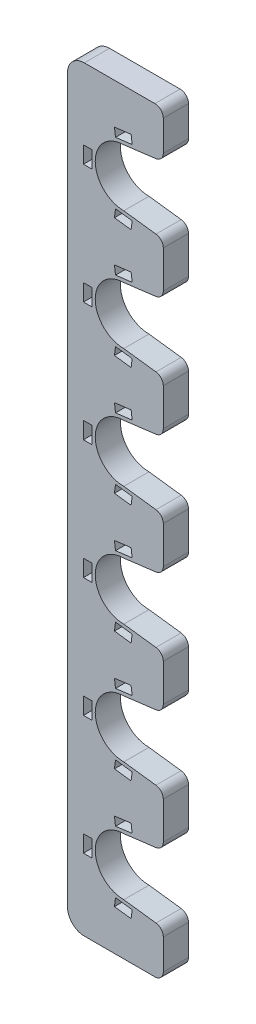
SolidWorks part; units mm, degrees
ref_plane "Front" through (0, 0, 0) normal (0, 0, 1) x (1, 0, 0)
ref_plane "Top" through (0, 0, 0) normal (0, 1, 0) x (1, 0, 0)
ref_plane "Right" through (0, 0, 0) normal (1, 0, 0) x (0, 0, -1)
sketch "Esquisse1" plane through (0, 0, 0) normal (0, 0, 1) x (1, 0, 0)
  line L1 (0, 0) -> (47, 0)
  line L2 (0, 0) -> (0, 450)
  line L3 (0, 450) -> (47, 450)
  line L4 (47, 0) -> (47, 450)
  dimension "D1" = 47
  dimension "D2" = 450
extrude "Boss.-Extru.1" add sketch "Esquisse1" along normal blind 15
sketch "Esquisse2" plane through (0, 0, 15) normal (0, 0, 1) x (1, 0, 0)
  line L0 (23.5, 0) -> (23.5, 450) construction
  line L1 (0, 0) -> (47, 0) construction
  line L2 (47, 450) -> (0, 450) construction
  line L3 (23.5, 225) -> (0, 225) construction
  line L4 (23.5, 154) -> (0, 154) construction
  line L5 (0, 450) -> (0, 0) construction
  line L6 (23.5, 83) -> (0, 83) construction
  line L7 (23.5, 367) -> (0, 367) construction
  line L8 (23.5, 296) -> (0, 296) construction
  circle A0 centre (23.5, 260.5) radius 17
  circle A1 centre (23.5, 189.5) radius 17
  circle A2 centre (23.5, 118.5) radius 17
  circle A3 centre (23.5, 47.5) radius 17
  circle A4 centre (23.5, 402.5) radius 17
  circle A5 centre (23.5, 331.5) radius 17
  dimension "D1" = 71
  dimension "D2" = 34
  dimension "D3" = 71
  dimension "D4" = 71
extrude "Enlèv. mat.-Extru.1" cut sketch "Esquisse2" against normal through all both and the other way through all
sketch "Esquisse3" plane through (0, 0, 15) normal (0, 0, 1) x (1, 0, 0)
  line L0 (23.5, 189.5) -> (23.5, 260.5) construction
  line L1 (23.5, 225) -> (0, 225) construction
  line L2 (0, 450) -> (0, 0) construction
  line L3 (23.5, 243.5) -> (47, 240.5)
  line L4 (47, 0) -> (47, 450) construction
  line L5 (47, 240.5) -> (47, 280.5)
  line L6 (47, 260.5) -> (23.5, 260.5) construction
  line L7 (23.5, 277.5) -> (47, 280.5)
  line L8 (23.5, 243.5) -> (23.5, 277.5)
  line L9 (47, 189.5) -> (23.5, 189.5) construction
  line L10 (23.5, 172.5) -> (47, 169.5)
  line L11 (47, 209.5) -> (47, 169.5)
  line L12 (23.5, 206.5) -> (47, 209.5)
  line L13 (23.5, 206.5) -> (23.5, 172.5)
  line L14 (23.5, 172.5) -> (23.5, 135.5) construction
  line L15 (23.5, 64.5) -> (23.5, 101.5) construction
  line L16 (23.5, 83) -> (0, 83) construction
  line L17 (23.5, 154) -> (0, 154) construction
  line L18 (47, 118.5) -> (23.5, 118.5) construction
  line L19 (23.5, 101.5) -> (23.5, 135.5)
  line L20 (23.5, 101.5) -> (47, 98.5)
  line L21 (47, 98.5) -> (47, 138.5)
  line L22 (23.5, 135.5) -> (47, 138.5)
  line L23 (47, 47.5) -> (23.5, 47.5) construction
  line L24 (23.5, 30.5) -> (47, 27.5)
  line L25 (47, 67.5) -> (47, 27.5)
  line L26 (23.5, 64.5) -> (47, 67.5)
  line L27 (23.5, 64.5) -> (23.5, 30.5)
  line L28 (47, 402.5) -> (23.5, 402.5) construction
  line L29 (47, 331.5) -> (23.5, 331.5) construction
  line L30 (23.5, 296) -> (0, 296) construction
  line L31 (23.5, 367) -> (0, 367) construction
  line L32 (23.5, 385.5) -> (23.5, 348.5) construction
  line L33 (23.5, 385.5) -> (23.5, 419.5)
  line L34 (23.5, 385.5) -> (47, 382.5)
  line L35 (47, 382.5) -> (47, 422.5)
  line L36 (23.5, 419.5) -> (47, 422.5)
  line L37 (23.5, 314.5) -> (47, 311.5)
  line L38 (47, 351.5) -> (47, 311.5)
  line L39 (23.5, 348.5) -> (47, 351.5)
  line L40 (23.5, 348.5) -> (23.5, 314.5)
  circle A0 centre (23.5, 260.5) radius 17 construction
  circle A1 centre (23.5, 118.5) radius 17 construction
  circle A2 centre (23.5, 47.5) radius 17 construction
  dimension "D1" = 3
extrude "Enlèv. mat.-Extru.2" cut sketch "Esquisse3" against normal through all both and the other way through all
sketch "Esquisse4" plane through (0, 0, 15) normal (0, 0, 1) x (1, 0, 0)
  line L0 (47, 450) -> (0, 450) construction
  line L1 (0, 0) -> (-10, 0)
  line L2 (0, 0) -> (0, 450)
  line L3 (0, 450) -> (-10, 450)
  line L4 (-10, 0) -> (-10, 450)
  dimension "D1" = 10
extrude "Boss.-Extru.2" add sketch "Esquisse4" against normal up to vertex (15 mm away) up to point (0, 450, 0)
sketch "Esquisse5" plane through (0, 0, 15) normal (0, 0, 1) x (1, 0, 0)
  line L0 (47, 367) -> (-10, 367) construction
  line L1 (47, 351.5) -> (47, 382.5) construction
  line L2 (-10, 450) -> (-10, 0) construction
  line L3 (47, 296) -> (-10, 296) construction
  line L4 (47, 280.5) -> (47, 311.5) construction
  line L5 (47, 225) -> (-10, 225) construction
  line L6 (47, 209.5) -> (47, 240.5) construction
  line L7 (47, 154) -> (-10, 154) construction
  line L8 (47, 138.5) -> (47, 169.5) construction
  line L9 (47, 83) -> (-10, 83) construction
  line L10 (47, 67.5) -> (47, 98.5) construction
  line L11 (4.5, 189.5) -> (6.5, 189.5) construction
  line L12 (-0.5, 194.5) -> (4.5, 194.5)
  line L13 (-0.5, 194.5) -> (-0.5, 184.5)
  line L14 (-0.5, 184.5) -> (4.5, 184.5)
  line L15 (4.5, 194.5) -> (4.5, 184.5)
  line L16 (47, 169.5) -> (47, 209.5) construction
  line L17 (47, 189.5) -> (6.5, 189.5) construction
  line L18 (18.564, 207.8861) -> (28.4835, 209.1524)
  line L19 (23.5, 206.5) -> (47, 209.5) construction
  line L20 (18.564, 207.8861) -> (17.9308, 212.8458)
  line L21 (17.9308, 212.8458) -> (27.8503, 214.1122)
  line L22 (27.8503, 214.1122) -> (28.4835, 209.1524)
  line L23 (18.564, 207.8861) -> (26.75, 189.5) construction
  line L24 (27.8503, 164.8878) -> (28.4835, 169.8476)
  line L25 (17.9308, 166.1542) -> (27.8503, 164.8878)
  line L26 (18.564, 171.1139) -> (17.9308, 166.1542)
  line L27 (18.564, 171.1139) -> (28.4835, 169.8476)
  line L28 (18.564, 100.1139) -> (26.75, 118.5) construction
  line L29 (47, 118.5) -> (6.5, 118.5) construction
  line L30 (47, 138.5) -> (47, 98.5) construction
  line L31 (4.5, 118.5) -> (6.5, 118.5) construction
  line L32 (18.564, 136.8861) -> (28.4835, 138.1524)
  line L33 (18.564, 136.8861) -> (17.9308, 141.8458)
  line L34 (17.9308, 141.8458) -> (27.8503, 143.1122)
  line L35 (27.8503, 143.1122) -> (28.4835, 138.1524)
  line L36 (27.8503, 93.8878) -> (28.4835, 98.8476)
  line L37 (17.9308, 95.1542) -> (27.8503, 93.8878)
  line L38 (18.564, 100.1139) -> (17.9308, 95.1542)
  line L39 (18.564, 100.1139) -> (28.4835, 98.8476)
  line L40 (4.5, 113.5) -> (4.5, 123.5)
  line L41 (-0.5, 123.5) -> (4.5, 123.5)
  line L42 (-0.5, 113.5) -> (-0.5, 123.5)
  line L43 (-0.5, 113.5) -> (4.5, 113.5)
  line L44 (4.5, 47.5) -> (6.5, 47.5) construction
  line L45 (47, 27.5) -> (47, 67.5) construction
  line L46 (47, 47.5) -> (6.5, 47.5) construction
  line L47 (18.564, 65.8861) -> (26.75, 47.5) construction
  line L48 (-0.5, 52.5) -> (4.5, 52.5)
  line L49 (-0.5, 52.5) -> (-0.5, 42.5)
  line L50 (-0.5, 42.5) -> (4.5, 42.5)
  line L51 (4.5, 52.5) -> (4.5, 42.5)
  line L52 (18.564, 65.8861) -> (28.4835, 67.1524)
  line L53 (18.564, 65.8861) -> (17.9308, 70.8458)
  line L54 (17.9308, 70.8458) -> (27.8503, 72.1122)
  line L55 (27.8503, 72.1122) -> (28.4835, 67.1524)
  line L56 (27.8503, 22.8878) -> (28.4835, 27.8476)
  line L57 (17.9308, 24.1542) -> (27.8503, 22.8878)
  line L58 (18.564, 29.1139) -> (17.9308, 24.1542)
  line L59 (18.564, 29.1139) -> (28.4835, 27.8476)
  line L60 (18.564, 384.1139) -> (26.75, 402.5) construction
  line L61 (47, 402.5) -> (6.5, 402.5) construction
  line L62 (47, 422.5) -> (47, 382.5) construction
  line L63 (4.5, 402.5) -> (6.5, 402.5) construction
  line L64 (4.5, 331.5) -> (6.5, 331.5) construction
  line L65 (47, 311.5) -> (47, 351.5) construction
  line L66 (47, 331.5) -> (6.5, 331.5) construction
  line L67 (18.564, 349.8861) -> (26.75, 331.5) construction
  line L68 (18.564, 242.1139) -> (26.75, 260.5) construction
  line L69 (47, 260.5) -> (6.5, 260.5) construction
  line L70 (47, 280.5) -> (47, 240.5) construction
  line L71 (4.5, 260.5) -> (6.5, 260.5) construction
  line L72 (47, 367) -> (-10, 367) construction
  line L73 (47, 296) -> (-10, 296) construction
  line L74 (18.564, 420.8861) -> (28.4835, 422.1524)
  line L75 (18.564, 420.8861) -> (17.9308, 425.8458)
  line L76 (17.9308, 425.8458) -> (27.8503, 427.1122)
  line L77 (27.8503, 427.1122) -> (28.4835, 422.1524)
  line L78 (27.8503, 377.8878) -> (28.4835, 382.8476)
  line L79 (17.9308, 379.1542) -> (27.8503, 377.8878)
  line L80 (18.564, 384.1139) -> (17.9308, 379.1542)
  line L81 (18.564, 384.1139) -> (28.4835, 382.8476)
  line L82 (4.5, 397.5) -> (4.5, 407.5)
  line L83 (-0.5, 407.5) -> (4.5, 407.5)
  line L84 (-0.5, 397.5) -> (-0.5, 407.5)
  line L85 (-0.5, 397.5) -> (4.5, 397.5)
  line L86 (-0.5, 336.5) -> (4.5, 336.5)
  line L87 (-0.5, 336.5) -> (-0.5, 326.5)
  line L88 (-0.5, 326.5) -> (4.5, 326.5)
  line L89 (4.5, 336.5) -> (4.5, 326.5)
  line L90 (18.564, 349.8861) -> (28.4835, 351.1524)
  line L91 (18.564, 349.8861) -> (17.9308, 354.8458)
  line L92 (17.9308, 354.8458) -> (27.8503, 356.1122)
  line L93 (27.8503, 356.1122) -> (28.4835, 351.1524)
  line L94 (27.8503, 306.8878) -> (28.4835, 311.8476)
  line L95 (17.9308, 308.1542) -> (27.8503, 306.8878)
  line L96 (18.564, 313.1139) -> (17.9308, 308.1542)
  line L97 (18.564, 313.1139) -> (28.4835, 311.8476)
  line L98 (18.564, 278.8861) -> (28.4835, 280.1524)
  line L99 (18.564, 278.8861) -> (17.9308, 283.8458)
  line L100 (17.9308, 283.8458) -> (27.8503, 285.1122)
  line L101 (27.8503, 285.1122) -> (28.4835, 280.1524)
  line L102 (27.8503, 235.8878) -> (28.4835, 240.8476)
  line L103 (17.9308, 237.1542) -> (27.8503, 235.8878)
  line L104 (18.564, 242.1139) -> (17.9308, 237.1542)
  line L105 (18.564, 242.1139) -> (28.4835, 240.8476)
  line L106 (4.5, 255.5) -> (4.5, 265.5)
  line L107 (-0.5, 265.5) -> (4.5, 265.5)
  line L108 (-0.5, 255.5) -> (-0.5, 265.5)
  line L109 (-0.5, 255.5) -> (4.5, 255.5)
  arc A1 (23.5, 206.5) -> (23.5, 172.5) centre (23.5, 189.5) ccw construction
  point P41 (17.2776, 211.8317)
  point P45 (20.8797, 206.0855)
  dimension "D1" = 5
  dimension "D2" = 10
  dimension "D3" = 2
  dimension "D4" = 10
  dimension "D5" = 5
  dimension "D6" = 2
  dimension "D7" = 66
extrude "Enlèv. mat.-Extru.3" cut sketch "Esquisse5" against normal blind 10
fillet "Congé1" radius 5 14 edges at (47, 422.5, 7.5) (47, 382.5, 7.5) (47, 351.5, 7.5) (47, 311.5, 7.5) (47, 280.5, 7.5) (47, 240.5, 7.5) (47, 209.5, 7.5) (47, 169.5, 7.5) (47, 138.5, 7.5) (47, 98.5, 7.5) (47, 67.5, 7.5) (47, 27.5, 7.5) (47, 450, 7.5) (47, 0, 7.5)
fillet "Congé2" radius 10 2 edges at (-10, 450, 7.5) (-10, 0, 7.5)
